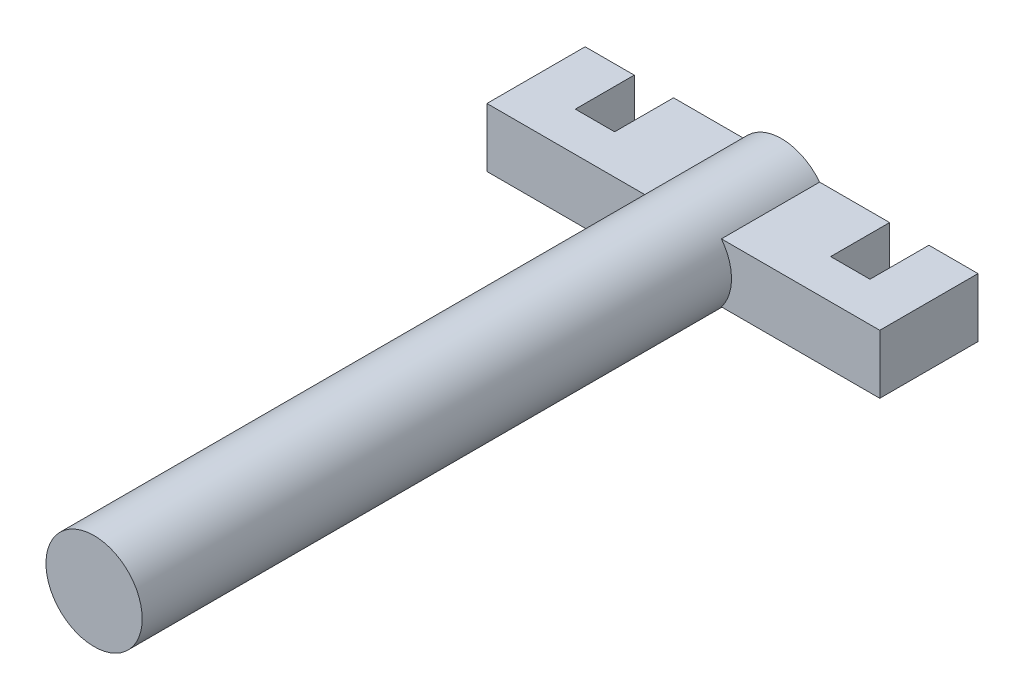
SolidWorks part; units mm, degrees
ref_plane "Front Plane" through (0, 0, 0) normal (0, 0, 1) x (1, 0, 0)
ref_plane "Top Plane" through (0, 0, 0) normal (0, 1, 0) x (1, 0, 0)
ref_plane "Right Plane" through (0, 0, 0) normal (1, 0, 0) x (0, 0, -1)
sketch "Sketch2" plane through (0, 0, 0) normal (0, 0, 1) x (1, 0, 0)
  circle A0 centre (0, 0) radius 2.45
  dimension "D1" = 4.9
extrude "Boss-Extrude1" add sketch "Sketch2" along normal blind 35
sketch "Sketch3" plane through (0, 0, 0) normal (0, 0, -1) x (-1, 0, 0)
  line L0 (-10, 1.5) -> (10, 1.5)
  line L1 (10, 1.5) -> (10, -1.5)
  line L4 (-10, 1.5) -> (-10, -1.5)
  line L5 (-10, -1.5) -> (10, -1.5)
  circle A1 centre (0, 0) radius 2.45 construction
  point P3 (10, 0)
  point P5 (0, 1.5)
  dimension "D1" = 1.5
  dimension "D4" = 20
extrude "Boss-Extrude2" add sketch "Sketch3" against normal blind 5
sketch "Sketch4" plane through (0, 0, 0) normal (0, 0, -1) x (-1, 0, 0)
  line L0 (0, 2.45) -> (0, -2.45) construction
  line L1 (-10, -1.5) -> (-1.9371, -1.5) construction
  line L2 (-7.5, 1.5) -> (-5.5, 1.5)
  line L3 (-7.5, 1.5) -> (-7.5, -1.5)
  line L4 (-7.5, -1.5) -> (-5.5, -1.5)
  line L5 (-5.5, 1.5) -> (-5.5, -1.5)
  line L6 (-7.5, 1.5) -> (-5.5, -1.5) construction
  line L7 (-7.5, -1.5) -> (-5.5, 1.5) construction
  line L8 (-1.9371, 1.5) -> (-10, 1.5) construction
  line L9 (-10, 1.5) -> (-10, -1.5) construction
  line L10 (7.5, -1.5) -> (5.5, 1.5) construction
  line L11 (7.5, 1.5) -> (5.5, -1.5) construction
  line L12 (5.5, 1.5) -> (5.5, -1.5)
  line L13 (7.5, -1.5) -> (5.5, -1.5)
  line L14 (7.5, 1.5) -> (7.5, -1.5)
  line L15 (7.5, 1.5) -> (5.5, 1.5)
  point P8 (-6.5, 0)
  point P23 (6.5, 0)
  dimension "D1" = 2.5
  dimension "D2" = 2
extrude "Cut-Extrude1" cut sketch "Sketch4" against normal offset from surface (3 mm away) 2 up to face at (6.0968, 0, 5)
sketch "Sketch5" plane through (0, 0, 0) normal (0, 1, 0) x (1, 0, 0)
  line L0 (-1.9371, 0) -> (-0.6294, 1.2879)
  line L2 (-0.6294, 1.2879) -> (0.6294, 1.2879)
  line L3 (0.6294, 1.2879) -> (1.9371, 0)
  line L5 (-1.9371, 0) -> (-5.5, 0)
  line L6 (-5.5, 0) -> (-2.1615, 3.2879)
  line L7 (-2.1615, 3.2879) -> (2.1615, 3.2879)
  line L8 (2.1615, 3.2879) -> (5.5, 0)
  line L9 (1.9371, 0) -> (5.5, 0)
  dimension "D2" = 2
  dimension "D3" = 2.5
extrude "Boss-Extrude3" [suppressed] add sketch "Sketch5" along normal up to surface and the other way up to surface up to face at (6.2343, 1.5, 2) other way up to face at (6.2343, -1.5, 2)
